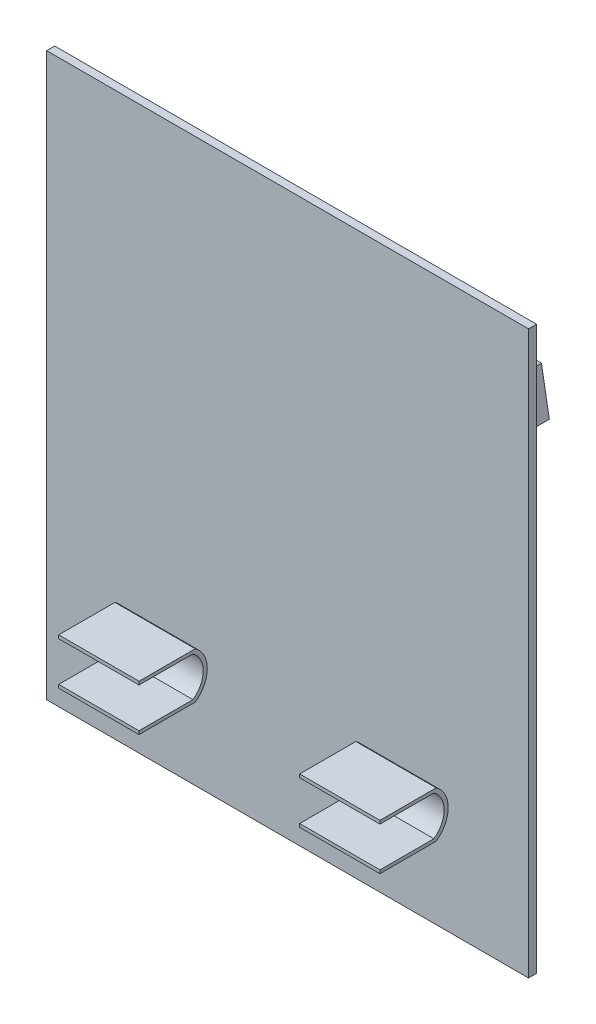
SolidWorks part; units mm, degrees
ref_plane "Front Plane" through (0, 0, 0) normal (0, 0, 1) x (1, 0, 0)
ref_plane "Top Plane" through (0, 0, 0) normal (0, 1, 0) x (1, 0, 0)
ref_plane "Right Plane" through (0, 0, 0) normal (1, 0, 0) x (0, 0, -1)
sketch "Sketch1" plane through (0, 0, 0) normal (0, 0, 1) x (1, 0, 0)
  line L1 (0, 0) -> (120, 0)
  line L2 (0, 0) -> (0, 140)
  line L3 (0, 140) -> (120, 140)
  line L4 (120, 0) -> (120, 140)
  dimension "D1" = 140
  dimension "D2" = 120
extrude "Boss-Extrude1" add sketch "Sketch1" along normal blind 9
sketch "Sketch3" plane through (120, 0, 0) normal (1, 0, 0) x (0, 0, -1)
  line L0 (-4.5, 0) -> (-4.5, 21) construction
  line L1 (-9, 0) -> (0, 0) construction
  line L3 (-9, 21) -> (0, 21)
  line L4 (-9, 21) -> (-9, 0)
  line L5 (-9, 0) -> (0, 0)
  line L6 (0, 21) -> (0, 0)
  line L7 (-9, 21) -> (0, 0) construction
  line L8 (-9, 0) -> (0, 21) construction
  line L17 (-12.5724, 21.82) -> (-26, 21.82)
  line L19 (-26, 31.685) -> (-12.5724, 31.685)
  line L20 (-26, 32.505) -> (-26, 31.685)
  line L21 (-26, 21.82) -> (-26, 21)
  line L22 (-12, 21) -> (-26, 21)
  line L23 (-12, 32.505) -> (-26, 32.505)
  arc A0 (-12, 21) -> (-12, 32.505) centre (-16.0152, 26.7525) ccw
  arc A1 (-12.5724, 21.82) -> (-12.5724, 31.685) centre (-16.0152, 26.7525) ccw
  point P4 (-4.5, 10.5)
  dimension "D4" = 1
  dimension "D1" = 21
extrude "Boss-Extrude2" add sketch "Sketch3" against normal blind 120
sketch "Sketch4" plane through (120, 0, 0) normal (1, 0, 0) x (0, 0, -1)
  line L0 (-9, 0) -> (-9, 140) construction
  line L1 (-9, 32.505) -> (-26, 32.505)
  line L2 (-9, 32.505) -> (-9, 21)
  line L3 (-9, 21) -> (-26, 21)
  line L4 (-26, 32.505) -> (-26, 21)
extrude "Cut-Extrude1" cut sketch "Sketch4" against normal blind 20
sketch "Sketch5" plane through (0, 0, 0) normal (-1, 0, 0) x (0, 0, 1)
  line L0 (9, 140) -> (9, 0) construction
  line L1 (9, 32.7033) -> (26, 32.7033)
  line L2 (9, 32.7033) -> (9, 21)
  line L3 (9, 21) -> (26, 21)
  line L4 (26, 32.7033) -> (26, 21)
extrude "Cut-Extrude2" cut sketch "Sketch5" against normal blind 20
sketch "Sketch6" plane through (0, 0, 0) normal (0, -1, 0) x (1, 0, 0)
  line L0 (20, 19) -> (100, 19) construction
  line L1 (20, 12) -> (20, 26) construction
  line L2 (100, 26) -> (100, 12) construction
  line L3 (0, 9) -> (120, 9) construction
  line L4 (20, 26) -> (40, 26)
  line L5 (20, 26) -> (20, 9)
  line L6 (20, 9) -> (40, 9)
  line L7 (40, 26) -> (40, 9)
  line L9 (100, 26) -> (80, 26)
  line L10 (100, 26) -> (100, 9)
  line L11 (100, 9) -> (80, 9)
  line L12 (80, 26) -> (80, 9)
  line L13 (40, 26) -> (80, 26)
  line L14 (40, 26) -> (40, 9)
  line L15 (40, 9) -> (80, 9)
  line L16 (80, 26) -> (80, 9)
  line M9 (120, 9) -> (0, 9)
  dimension "D1" = 20
  dimension "D2" = 20
extrude "Cut-Extrude3" cut sketch "Sketch6" against normal blind 80 contours L7 L0 L12 L13 | L0 L14 L16 M9 region at (60, 0, 22.5) region at (60, 0, 14)
sketch "Sketch12" plane through (0, 0, 0) normal (0, 0, -1) x (-1, 0, 0)
  text T0 "F G P" font "@Adobe Gothic Std B" height in points 72
extrude "Boss-Extrude3" add sketch "Sketch12" along normal blind 1.15
sketch "Sketch13" plane through (0, 0, 0) normal (0, 0, -1) x (-1, 0, 0)
  line L1 (-120, 140) -> (0, 140)
  line L2 (-120, 140) -> (-120, 0)
  line L3 (-120, 0) -> (0, 0)
  line L4 (0, 140) -> (0, 0)
extrude "Cut-Extrude4" cut sketch "Sketch13" along normal blind 10
sketch "Sketch14" plane through (0, 0, 0) normal (0, 0, -1) x (-1, 0, 0)
  line L1 (-120, 140) -> (0, 140)
  line L2 (-120, 140) -> (-120, 0)
  line L3 (-120, 0) -> (0, 0)
  line L4 (0, 140) -> (0, 0)
extrude "Cut-Extrude5" cut sketch "Sketch14" against normal blind 7
sketch "Sketch15" plane through (0, 0, 7) normal (0, 0, -1) x (-1, 0, 0)
  text T0 "FEROZE GANDHI \r\n   INSTITUTE OF \r\n  ENGINEERING \r\n          AND\r\n TECHNOLOGY\r\n           RBL" font "@Adobe Gothic Std B" height in points 36
extrude "Boss-Extrude4" add sketch "Sketch15" along normal blind 10
